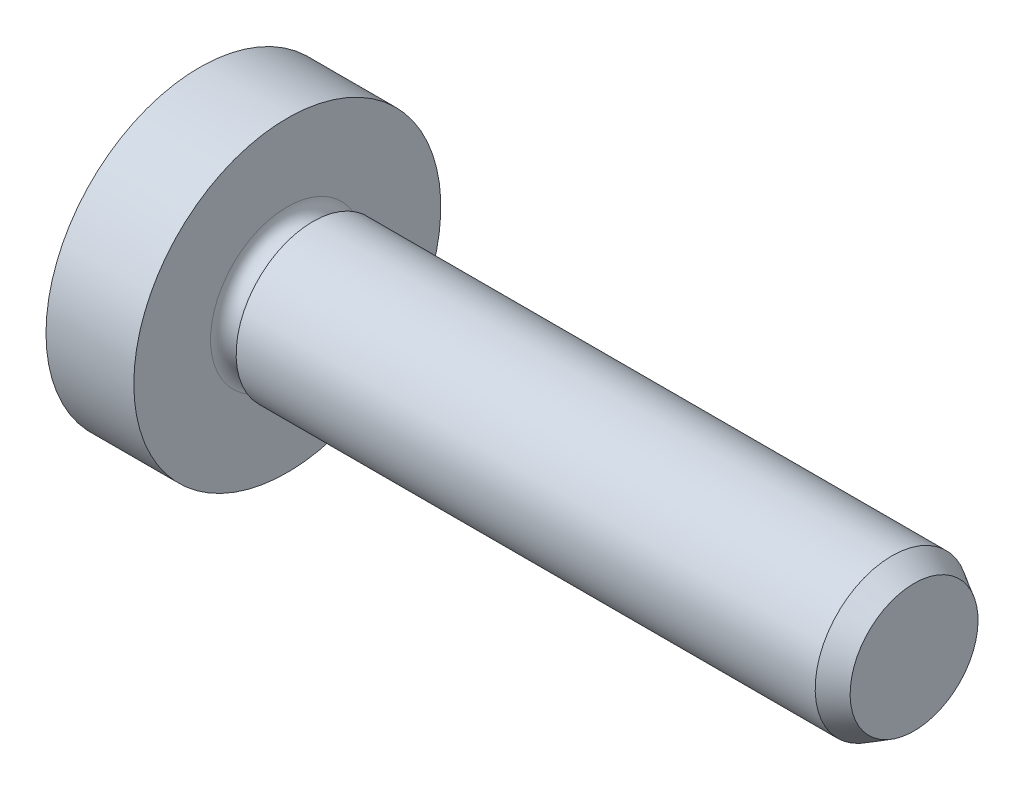
SolidWorks part; units mm, degrees
ref_plane "Front" through (0, 0, 0) normal (0, 0, 1) x (1, 0, 0)
ref_plane "Top" through (0, 0, 0) normal (0, 1, 0) x (1, 0, 0)
ref_plane "Right" through (0, 0, 0) normal (1, 0, 0) x (0, 0, -1)
sketch "Sketch1" plane through (0, 0, 0) normal (0, 0, 1) x (1, 0, 0)
  line L0 (-96.3852, 0) -> (11.3165, 0) construction
  line L1 (29.1, 0) -> (29.1, 3)
  line L2 (29.1, 3) -> (4.6, 3)
  line L3 (4.6, 3) -> (4.6, 6)
  line L4 (4.6, 6) -> (1.1676, 6)
  line L5 (29.1, 0) -> (0, 0)
  arc A0 (1.1676, 6) -> (0, 0) centre (16, 0) ccw
  dimension "l" = 24.5
revolve "Base" add sketch "Sketch1" angle 360 about L0
cosmetic thread "ThreadCosmetic1" [suppressed] parameters "D2"=5
sketch "Sketch2" plane through (0, 0, 0) normal (1, 0, 0) x (0, 0, -1)
  line L0 (6.5369, 0) -> (-7.0008, 0) construction
  line L1 (0, 6.811) -> (0, -6.4314) construction
  line L2 (-0.69, 3.45) -> (0.69, 3.45)
  line L3 (0.69, 3.45) -> (0.69, 0.69)
  line L4 (0.69, 0.69) -> (3.45, 0.69)
  line L5 (3.45, 0.69) -> (3.45, -0.69)
  line L6 (0.69, -0.69) -> (3.45, -0.69)
  line L7 (0.69, -3.45) -> (0.69, -0.69)
  line L8 (-0.69, -3.45) -> (0.69, -3.45)
  line L9 (-0.69, -3.45) -> (-0.69, -0.69)
  line L10 (-0.69, -0.69) -> (-3.45, -0.69)
  line L11 (-3.45, 0.69) -> (-3.45, -0.69)
  line L12 (-0.69, 0.69) -> (-3.45, 0.69)
  line L13 (-0.69, 3.45) -> (-0.69, 0.69)
  point P5 (-3.45, 0)
  point P11 (3.45, 0)
  point P15 (0, -3.45)
  point P20 (0, 3.45)
  dimension "D2" = 6.9
  dimension "D3" = 1.38
  dimension "D4" = 1.38
extrude "CrossRecess" cut sketch "Sketch2" along normal blind 3.1
draft "Draft1" type of draft neutral plane draft angle 30 neutral plane "Right" faces to draft 4 face at (1.742, 0, 3.45) face at (1.742, 3.45, 0) face at (1.742, 0, -3.45) face at (1.742, -3.45, 0) neutral plane through (0, 0, 0) neutral plane normal (1, 0, 0) reverse direction yes parameters "D1"=30
sketch "Sketch6" plane through (0, 0, 0) normal (0, 0, 1) x (1, 0, 0)
  line L0 (30.9483, 0) -> (0, 0) construction
  line L1 (29.1, -3) -> (29.1, 3) construction
  line L2 (28.234, -3) -> (29.1, -2.5)
  line L6 (29.1, -2.5) -> (29.1, -3)
  line L7 (29.1, -3) -> (28.234, -3)
  dimension "D2" = 5
  dimension "D1" = 30
  dimension "D3" = 6
revolve "BaseEnd" cut sketch "Sketch6" angle 360 about L0
sketch "Sketch4" plane through (0, 0, 0) normal (0, 1, 0) x (1, 0, 0)
  line L0 (14.876, 0) -> (0, 0) construction
  line L2 (4.6, 3) -> (5.6, 3)
  arc A0 (5.6, 3) -> (4.6, 3) centre (5.1, 3) cw
  dimension "a1" = 1
revolve "Cut-Revolve2" cut sketch "Sketch4" angle 360 about L0
sketch "Sketch7" plane through (0, 0, 0) normal (0, 0, 1) x (1, 0, 0)
  line L0 (0, 0) -> (30.1311, 0) construction
  line L1 (28.0896, 3.2887) -> (28.3783, 3.2887)
  line L2 (28.3783, 3.2887) -> (28.3783, 3)
  line L3 (28.3783, 3) -> (28.234, 2.75)
  line L4 (28.234, 2.75) -> (28.0896, 3)
  line L5 (28.0896, 3) -> (28.0896, 3.2887)
  line L6 (28.234, 3) -> (28.234, -3) construction
  dimension "D2" = 5.5
  dimension "D1" = 6
revolve "Cut-Revolve10" [suppressed] cut sketch "Sketch7" angle 360 about L0
pattern_linear "LPattern10" [suppressed] count 63 spacing 0.375 along (-1, 0, 0) of bodies 108
sketch "Sketch5" plane through (0, 0, 0) normal (0, 1, 0) x (1, 0, 0)
  line L0 (12.8957, 0) -> (-1.3597, 0) construction
  line L3 (4.6, 3) -> (14.1857, 3)
  line L4 (4.6, 3) -> (4.6, 2.9988)
  line L5 (4.8488, 2.75) -> (11.6857, 2.75)
  line L6 (11.6857, 2.75) -> (14.1857, 3)
  line L8 (29.1, -3) -> (29.1, 3) construction
  line L9 (4.6, -6) -> (4.6, 6) construction
  arc A0 (4.6, 2.9988) -> (4.8488, 2.75) centre (4.8488, 2.9988) ccw
  dimension "D3" = 0.2488
  dimension "D2" = 5.5
  dimension "D1" = 6
  dimension "b" = 14.9143
revolve "Cut-Revolve3" [suppressed] cut sketch "Sketch5" angle 360 about L0
equation "\"D3@Sketch2\" = \"m@Sketch2\" / 5"
equation "\"D4@Sketch2\" = \"D3@Sketch2\""
equation "\"D2@Sketch2\" = \"m@Sketch2\""
equation "\"D2@ThreadCosmetic1\" = \"st@Sketch1\" - 1"
equation "\"D2@Sketch5\" = \"D2@ThreadCosmetic1\"+0.5"
equation "\"D2@Sketch6\" = \"D2@ThreadCosmetic1\""
equation "\"D1@Sketch5\" = \"st@Sketch1\""
equation "\"D3@Sketch6\" = \"st@Sketch1\""
equation "\"D3@Sketch5\" =  ( \"D1@Sketch5\" - \"D2@Sketch5\" )  / 2.01"
equation "\"D2@Sketch7\" = \"D2@ThreadCosmetic1\"+0.5"
equation "\"D1@Sketch7\" = \"st@Sketch1\""
equation "\"D3@LPattern10\" =  ( \"D1@Sketch7\" - \"D2@Sketch7\" )  / 2 * 1.5"
equation "\"D1@LPattern10\" = (  \"l@Sketch1\" - ( \"D3@Sketch6\"- \"D2@Sketch6\" )  / 2 *  1.732   )  / \"D3@LPattern10\""
